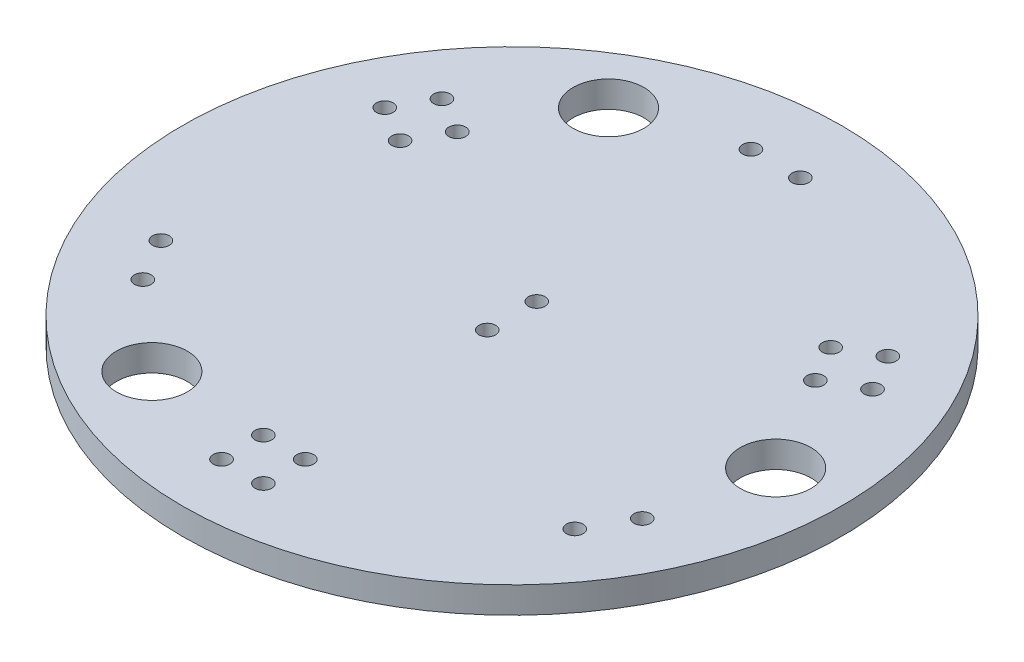
SolidWorks part; units mm, degrees
ref_plane "Front Plane" through (0, 0, 0) normal (0, 0, 1) x (1, 0, 0)
ref_plane "Top Plane" through (0, 0, 0) normal (0, 1, 0) x (1, 0, 0)
ref_plane "Right Plane" through (0, 0, 0) normal (1, 0, 0) x (0, 0, -1)
sketch "Sketch1" plane through (0, 0, 0) normal (0, 1, 0) x (1, 0, 0)
  circle A0 centre (0, 0) radius 20
  dimension "D1" = 40
extrude "Boss-Extrude1" add sketch "Sketch1" along normal blind 1.6
sketch "Sketch2" plane through (0, 1.6, 0) normal (0, 1, 0) x (1, 0, 0)
  line L0 (0, 0) -> (16, 0) construction
  circle A0 centre (16, 0) radius 2.15
  circle A2 centre (-8, -13.8564) radius 2.15
  circle A3 centre (-8, 13.8564) radius 2.15
  point P14 (0, 0)
  dimension "D1" = 16
  dimension "D2" = 4.3
  dimension "D3" = 3
extrude "Cut-Extrude1" cut sketch "Sketch2" against normal through all
ref_axis "Axis1" through (0, 1.6, 0) along (0, -1, 0)
ref_plane "Plane1" through (0, 0, 0) normal (0.866, 0, 0.5) x (0, -1, 0)
sketch "Sketch3" plane through (0, 1.6, 0) normal (0, 1, 0) x (1, 0, 0)
  circle A0 centre (-1.27, -13.817) radius 0.508
  circle A1 centre (-1.27, -16.357) radius 0.508
  circle A3 centre (1.27, -13.817) radius 0.508
  circle A4 centre (1.27, -16.357) radius 0.508
  circle A8 centre (-11.3309, 8.0084) radius 0.508
  circle A9 centre (-13.5306, 9.2784) radius 0.508
  circle A11 centre (-12.6009, 5.8086) radius 0.508
  circle A12 centre (-14.8006, 7.0786) radius 0.508
  circle A16 centre (12.6009, 5.8086) radius 0.508
  circle A17 centre (14.8006, 7.0786) radius 0.508
  circle A19 centre (11.3309, 8.0084) radius 0.508
  circle A20 centre (13.5306, 9.2784) radius 0.508
  circle A24 centre (0, 1.5) radius 0.508
  circle A25 centre (0, 1.5) radius 0.25 construction
  circle A26 centre (0, -1.5) radius 0.508
  circle A27 centre (0, -1.5) radius 0.25 construction
  circle A43 centre (1.5, 16) radius 0.508
  circle A44 centre (1.5, 16) radius 0.9 construction
  circle A45 centre (-1.5, 16) radius 0.508
  circle A46 centre (-1.5, 16) radius 0.9 construction
  circle A47 centre (13.1064, -9.299) radius 0.508
  circle A48 centre (14.6064, -6.701) radius 0.508
  circle A49 centre (-14.6064, -6.701) radius 0.508
  circle A50 centre (-13.1064, -9.299) radius 0.508
  point P4 (11.5546, 12.3931)
  point P6 (-16.51, 3.81)
  point P8 (-1.27, -16.357)
  point P10 (-1.27, -13.817)
  point P12 (1.27, -13.817)
  point P14 (1.27, -16.357)
  point P34 (-13.5306, 9.2784)
  point P35 (-11.3309, 8.0084)
  point P38 (-12.6009, 5.8086)
  point P41 (-14.8006, 7.0786)
  point P54 (0, 0)
  point P62 (14.8006, 7.0786)
  point P63 (12.6009, 5.8086)
  point P64 (11.3309, 8.0084)
  point P65 (13.5306, 9.2784)
  point P82 (0, 0)
  dimension "D1" = 1.016
  dimension "D2" = 3
extrude "Cut-Extrude2" cut sketch "Sketch3" against normal through all
